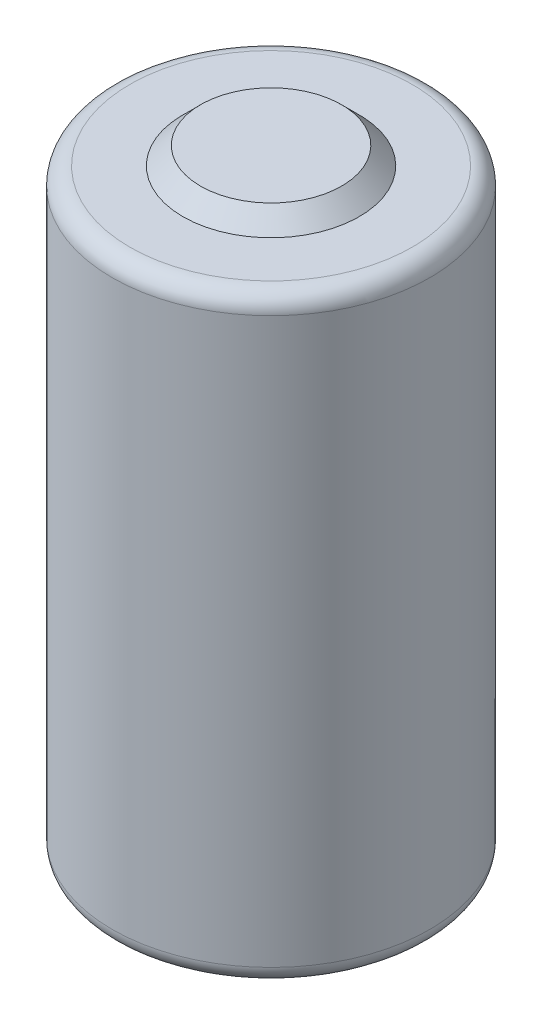
SolidWorks part; units mm, degrees
ref_plane "Front Plane" through (0, 0, 0) normal (0, 0, 1) x (1, 0, 0)
ref_plane "Top Plane" through (0, 0, 0) normal (0, 1, 0) x (1, 0, 0)
ref_plane "Right Plane" through (0, 0, 0) normal (1, 0, 0) x (0, 0, -1)
sketch "Sketch1" plane through (0, 0, 0) normal (0, 1, 0) x (1, 0, 0)
  circle A0 centre (0, 0) radius 9
  dimension "D1" = 18
extrude "Boss-Extrude1" add sketch "Sketch1" along normal blind 34
sketch "Sketch2" plane through (0, 34, 0) normal (0, 1, 0) x (1, 0, 0)
  circle A0 centre (0, 0) radius 4
  dimension "D1" = 8
extrude "Boss-Extrude2" add sketch "Sketch2" along normal blind 1
fillet "Fillet1" radius 1 2 edges at (0, 0, 9) (0, 34, 9)
chamfer "Chamfer1" distance 1 angle 45 1 edges at (0, 34, 4)
